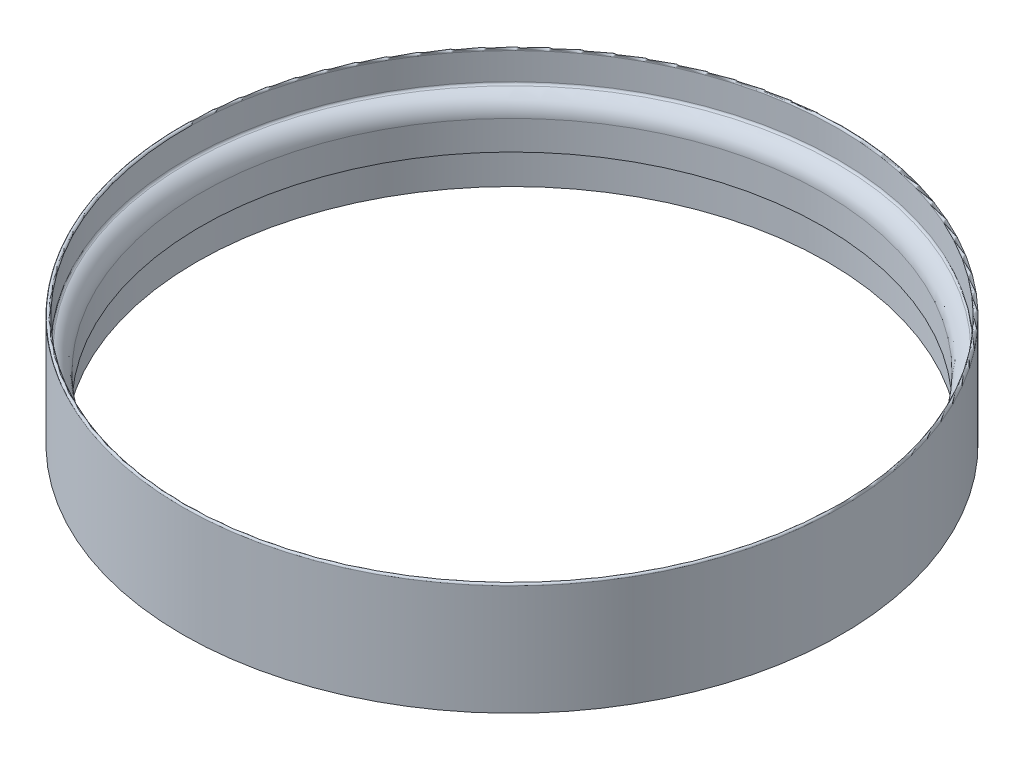
SolidWorks part; units mm, degrees
ref_plane "Front Plane" through (0, 0, 0) normal (0, 0, 1) x (1, 0, 0)
ref_plane "Top Plane" through (0, 0, 0) normal (0, 1, 0) x (1, 0, 0)
ref_plane "Right Plane" through (0, 0, 0) normal (1, 0, 0) x (0, 0, -1)
sketch "Sketch1" plane through (0, 0, 0) normal (1, 0, 0) x (0, 0, -1)
  line L0 (0, 0) -> (0, 21.8072) construction
  line L1 (-104.902, 0) -> (-100.457, 0)
  line L2 (-100.457, 0) -> (-100.457, 10.5)
  line L3 (-100.457, 10.5) -> (-99.06, 10.5)
  line L4 (-99.06, 10.5) -> (-99.06, 19.771)
  line L5 (-99.06, 19.771) -> (-103.8225, 19.771) construction
  line L6 (-103.8225, 19.771) -> (-103.8225, 35.646) construction
  line L7 (-103.8225, 35.646) -> (-104.902, 35.646)
  line L8 (-104.902, 35.646) -> (-104.902, 0)
  line L9 (-103.8225, 25.9194) -> (-103.8225, 35.646)
  arc A0 (-99.06, 19.771) -> (-103.8225, 25.9194) centre (-105.41, 19.771) ccw
  dimension "D8" = 6.35
  dimension "D1" = 10.5
  dimension "D2" = 9.271
  dimension "D3" = 15.875
  dimension "D4" = 200.914
  dimension "D5" = 198.12
  dimension "D6" = 103.8225
  dimension "D7" = 209.804
revolve "Revolve1" add sketch "Sketch1" angle 360 about L0
fillet "Fillet1" radius 0.7937 2 edges at (0, 10.5, -100.457) (0, 25.9194, -103.8225)
fillet "Fillet2" 2 edges at (0, 35.646, -104.902) (0, 35.646, -103.8225) type full round first side face at (0, 0, -104.902) second side face at (0, 26.5062, -103.8225) middle face at (0, 35.646, -104.902)
equation "\"bottom_bearing_thickness\"=0.413386"
equation "\"D1@Sketch1\"=\"bottom_bearing_thickness\""
equation "\"middle_thick\"=0.365"
equation "\"D2@Sketch1\"=\"middle_thick\""
equation "\"printer_limit\"=8.26"
equation "\"D7@Sketch1\"=\"printer_limit\""
